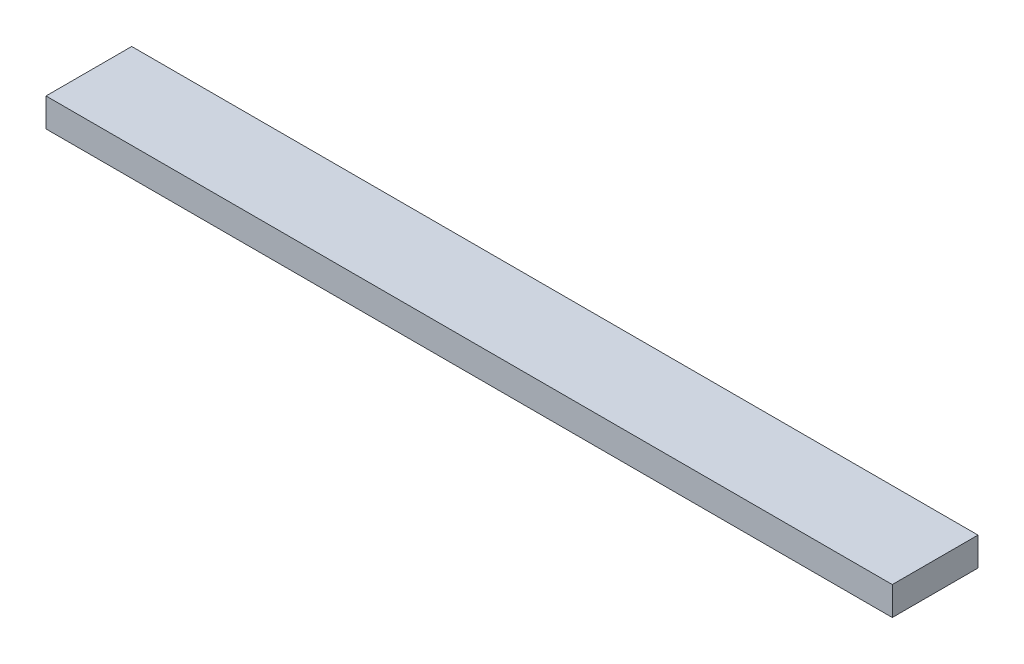
SolidWorks part; units mm, degrees
ref_plane "Front Plane" through (0, 0, 0) normal (0, 0, 1) x (1, 0, 0)
ref_plane "Top Plane" through (0, 0, 0) normal (0, 1, 0) x (1, 0, 0)
ref_plane "Right Plane" through (0, 0, 0) normal (1, 0, 0) x (0, 0, -1)
sketch "Sketch1" plane through (0, 0, 0) normal (1, 0, 0) x (0, 0, -1)
  line L1 (0, 0) -> (38.1, 0)
  line L2 (0, 0) -> (0, 12.7)
  line L3 (0, 12.7) -> (38.1, 12.7)
  line L4 (38.1, 0) -> (38.1, 12.7)
  dimension "D1" = 38.1
  dimension "D2" = 12.7
extrude "Boss-Extrude1" add sketch "Sketch1" along normal blind 376.2
